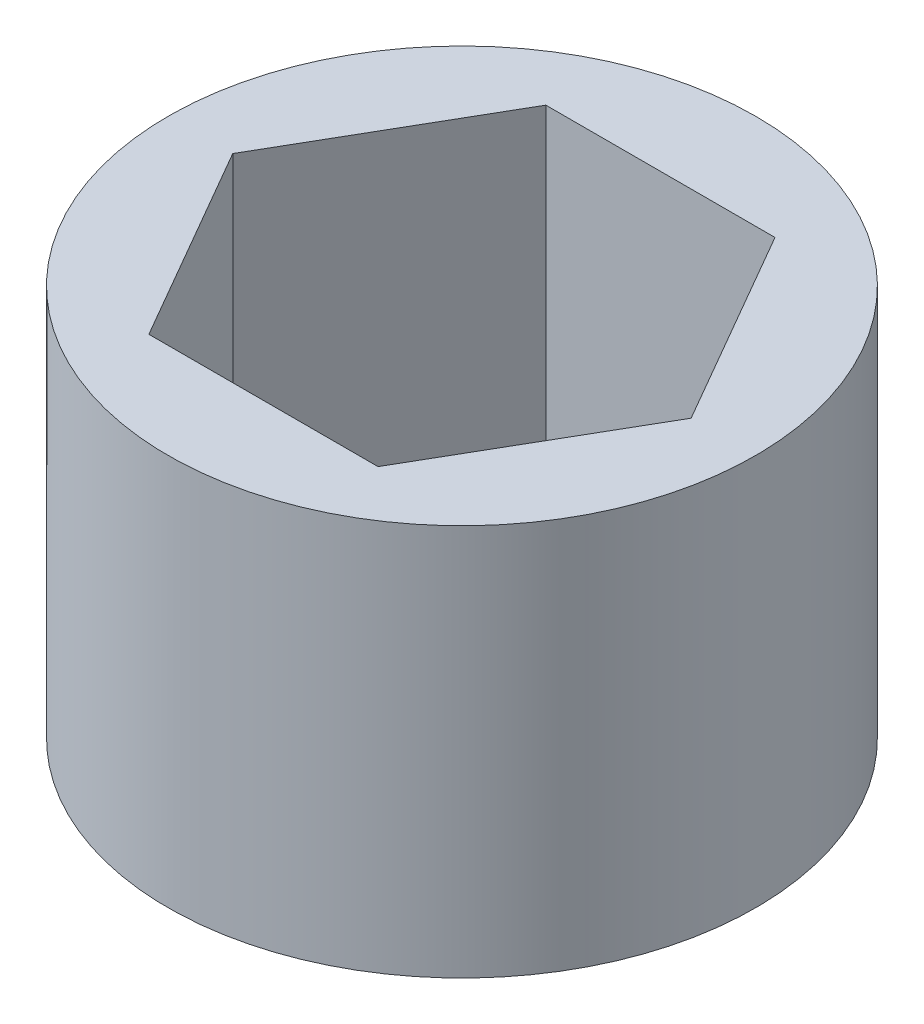
SolidWorks part; units mm, degrees
ref_plane "Front Plane" through (0, 0, 0) normal (0, 0, 1) x (1, 0, 0)
ref_plane "Top Plane" through (0, 0, 0) normal (0, 1, 0) x (1, 0, 0)
ref_plane "Right Plane" through (0, 0, 0) normal (1, 0, 0) x (0, 0, -1)
sketch "Sketch1" plane through (0, 0, 0) normal (0, 1, 0) x (1, 0, 0)
  line L1 (2.7863, -4.826) -> (5.5726, 0)
  line L2 (5.5726, 0) -> (2.7863, 4.826)
  line L3 (2.7863, 4.826) -> (-2.7863, 4.826)
  line L4 (-2.7863, 4.826) -> (-5.5726, 0)
  line L5 (-5.5726, 0) -> (-2.7863, -4.826)
  line L6 (-2.7863, -4.826) -> (2.7863, -4.826)
  circle A0 centre (0, 0) radius 7.1438
  circle A1 centre (0, 0) radius 4.826 construction
  dimension "D1" = 9.652
  dimension "D2" = 14.2875
extrude "Boss-Extrude1" add sketch "Sketch1" along normal mid plane 9.525
